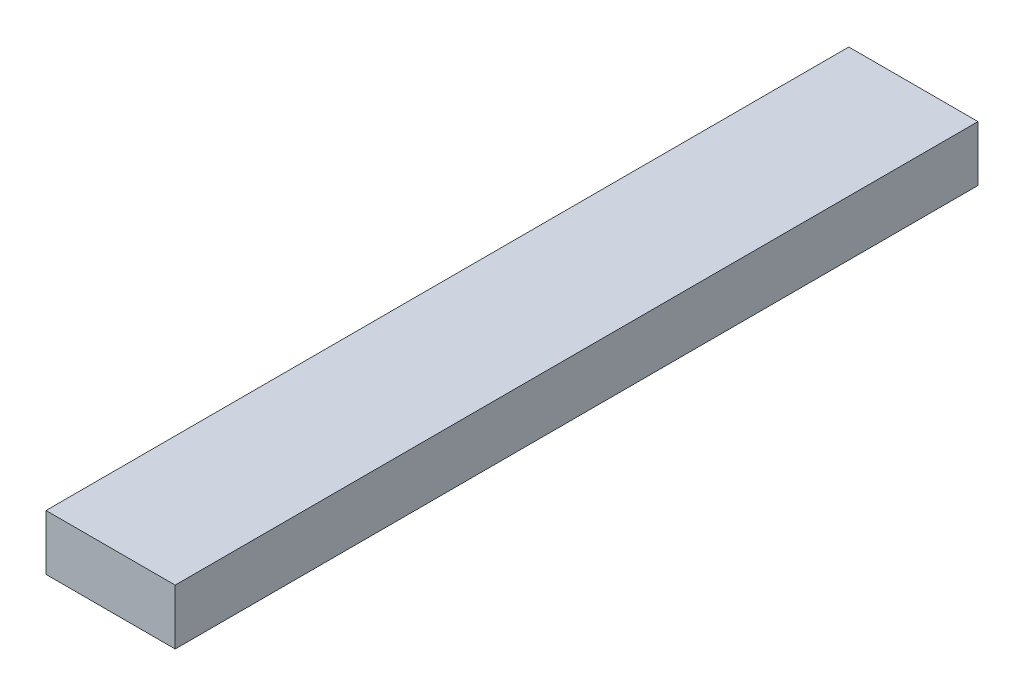
SolidWorks part; units mm, degrees
material "Pine"
ref_plane "Front Plane" through (0, 0, 0) normal (0, 0, 1) x (1, 0, 0)
ref_plane "Top Plane" through (0, 0, 0) normal (0, 1, 0) x (1, 0, 0)
ref_plane "Right Plane" through (0, 0, 0) normal (1, 0, 0) x (0, 0, -1)
sketch "Sketch1" plane through (0, 0, 0) normal (0, 0, 1) x (1, 0, 0)
  line L1 (0, 0) -> (88.9, 0)
  line L2 (0, 0) -> (0, 38.1)
  line L3 (0, 38.1) -> (88.9, 38.1)
  line L4 (88.9, 0) -> (88.9, 38.1)
  dimension "D1" = 88.9
  dimension "D2" = 38.1
extrude "Boss-Extrude1" add sketch "Sketch1" along normal blind 552.45
